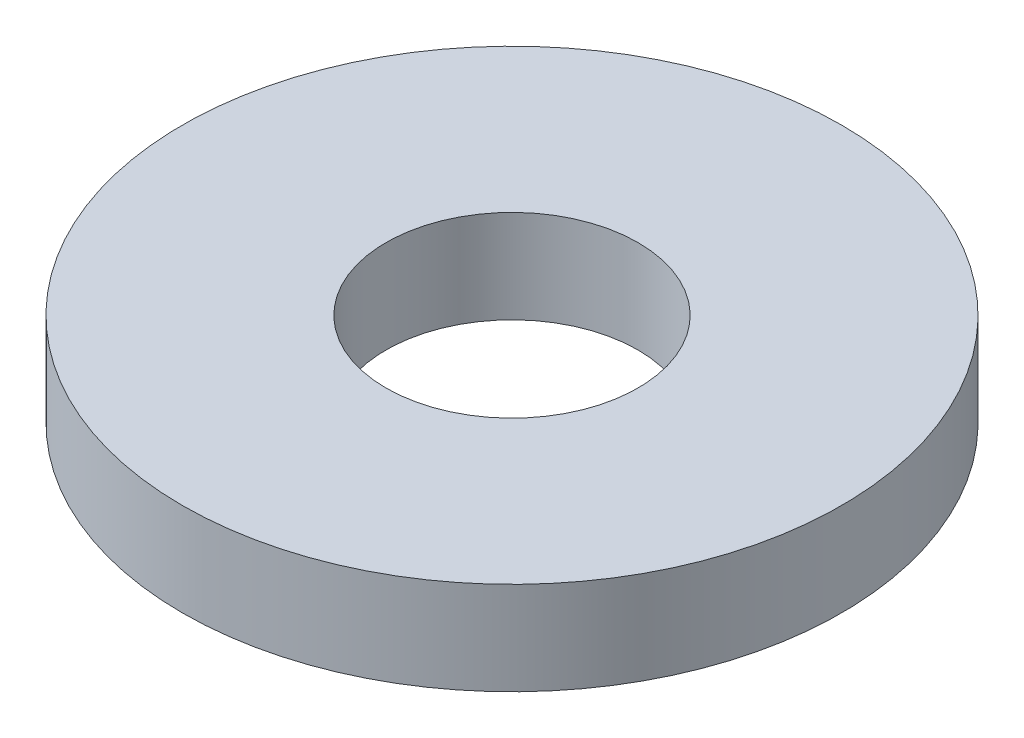
SolidWorks part; units mm, degrees
ref_plane "Front Plane" through (0, 0, 0) normal (0, 0, 1) x (1, 0, 0)
ref_plane "Top Plane" through (0, 0, 0) normal (0, 1, 0) x (1, 0, 0)
ref_plane "Right Plane" through (0, 0, 0) normal (1, 0, 0) x (0, 0, -1)
sketch "Sketch1" plane through (0, 0, 0) normal (0, 1, 0) x (1, 0, 0)
  circle A0 centre (0, 0) radius 85
  dimension "FLANGE_OD" = 170
extrude "Boss-Extrude1" add sketch "Sketch1" along normal blind 24
sketch "Sketch2" plane through (0, 0, 0) normal (0, 1, 0) x (1, 0, 0)
  circle A0 centre (0, 0) radius 32.5
  dimension "BORE_D" = 65
extrude "Cut-Extrude1" cut sketch "Sketch2" along normal through all
sketch "Sketch3" plane through (0, 24, 0) normal (0, 1, 0) x (1, 0, 0)
  circle A0 centre (0, 0) radius 22.2167 construction
  circle A1 centre (-22.2167, 0) radius 5.3725
  dimension "BOLT_D" = 10.7451
  dimension "BOLT_PCD" = 44.4334
extrude "Cut-Extrude2" cut sketch "Sketch3" against normal blind 23.8349 rebuild error yes
pattern_circular "CirPattern1" count 3 over 360 rebuild error yes
